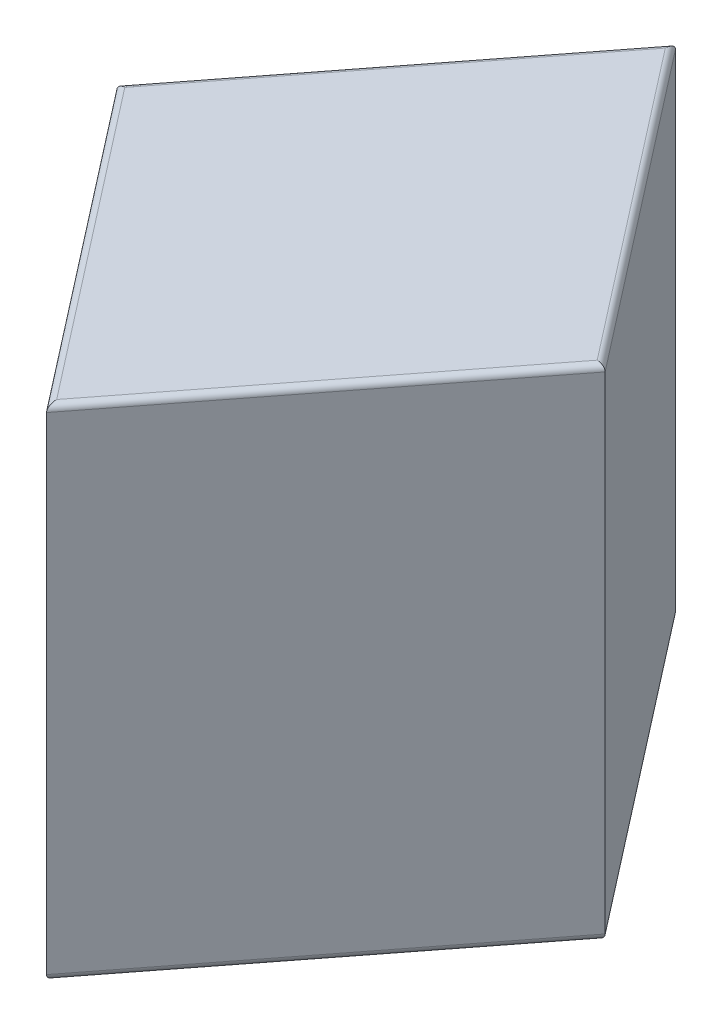
SolidWorks part; units mm, degrees
ref_plane "Front Plane" through (0, 0, 0) normal (0, 0, 1) x (1, 0, 0)
ref_plane "Top Plane" through (0, 0, 0) normal (0, 1, 0) x (1, 0, 0)
ref_plane "Right Plane" through (0, 0, 0) normal (1, 0, 0) x (0, 0, -1)
sketch "Sketch1" plane through (0, 0, 0) normal (0, 1, 0) x (1, 0, 0)
  line L0 (0, -25.2) -> (19.5594, 0)
  line L1 (0, -25.2) -> (-19.5594, 0)
  line L2 (19.5594, 0) -> (0, 25.2)
  line L3 (-19.5594, 0) -> (0, 25.2)
  line L4 (0, 0) -> (0, 88.0865) construction
  line L5 (0, 0) -> (44.8757, 0) construction
  dimension "D1" = 50.4
  dimension "D2" = 31.9
extrude "Boss-Extrude1" add sketch "Sketch1" along normal blind 40 contours L3 L2 L0 L1
fillet "Fillet1" radius 0.5 8 edges at (9.7797, 0, 12.6) (9.7797, 0, -12.6) (-9.7797, 0, -12.6) (-9.7797, 0, 12.6) (-9.7797, 40, -12.6) (9.7797, 40, -12.6) (9.7797, 40, 12.6) (-9.7797, 40, 12.6)
